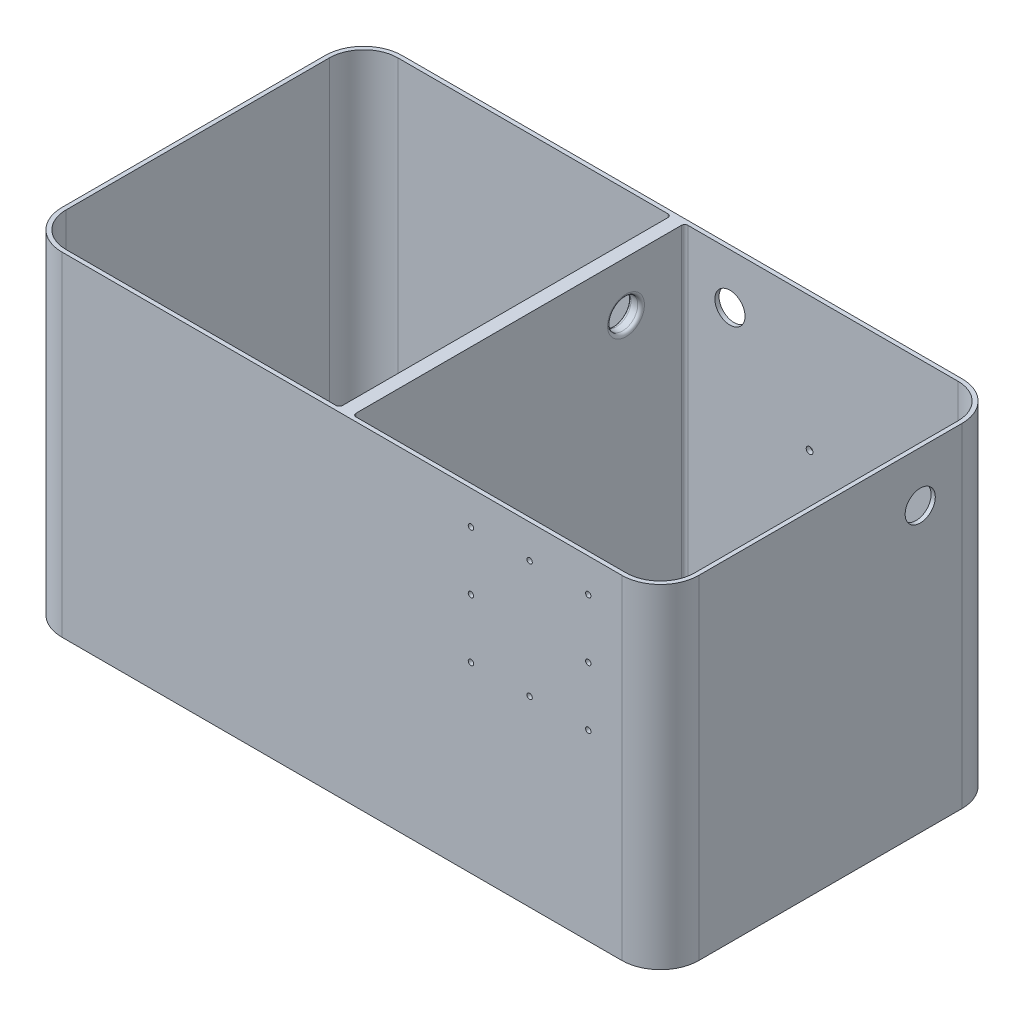
SolidWorks part; units mm, degrees
ref_plane "前视基准面" through (0, 0, 0) normal (0, 0, 1) x (1, 0, 0)
ref_plane "上视基准面" through (0, 0, 0) normal (0, 1, 0) x (1, 0, 0)
ref_plane "右视基准面" through (0, 0, 0) normal (1, 0, 0) x (0, 0, -1)
other "Configuration Table"
sketch "草图1" plane through (0, 0, 0) normal (0, 1, 0) x (1, 0, 0)
  line L1 (-167, 101.5) -> (167, 101.5)
  line L2 (-190, 78.5) -> (-190, -78.5)
  line L3 (-167, -101.5) -> (167, -101.5)
  line L4 (190, 78.5) -> (190, -78.5)
  line L5 (-190, 101.5) -> (190, -101.5) construction
  line L6 (-190, -101.5) -> (190, 101.5) construction
  arc A0 (167, -101.5) -> (190, -78.5) centre (167, -78.5) ccw
  arc A1 (167, 101.5) -> (190, 78.5) centre (167, 78.5) cw
  arc A2 (-190, -78.5) -> (-167, -101.5) centre (-167, -78.5) ccw
  arc A3 (-167, 101.5) -> (-190, 78.5) centre (-167, 78.5) ccw
  point P0 (0, 0)
  dimension "D3" = 23
  dimension "D1" = 380
  dimension "D2" = 203
extrude "凸台-拉伸1" add sketch "草图1" along normal blind 199
sketch "草图3" plane through (0, 199, 0) normal (0, 1, 0) x (1, 0, 0)
  line L0 (-190, 78.5) -> (-190, -78.5) construction
  line L1 (-167, 99) -> (167, 99)
  line L2 (-187.5, 78.5) -> (-187.5, -78.5)
  line L3 (-167, -99) -> (167, -99)
  line L4 (187.5, 78.5) -> (187.5, -78.5)
  line L5 (-187.5, 99) -> (187.5, -99) construction
  line L6 (-187.5, -99) -> (187.5, 99) construction
  line L7 (190, -78.5) -> (190, 78.5) construction
  arc A0 (-187.5, -78.5) -> (-167, -99) centre (-167, -78.5) ccw
  arc A1 (167, -99) -> (187.5, -78.5) centre (167, -78.5) ccw
  arc A2 (167, 99) -> (187.5, 78.5) centre (167, 78.5) cw
  arc A3 (-167, 99) -> (-187.5, 78.5) centre (-167, 78.5) ccw
  point P0 (0, 0)
  dimension "D5" = 20.5
  dimension "D1" = 198
  dimension "D2" = 375
  dimension "D3" = 2.5
  dimension "D4" = 2.5
extrude "切除-拉伸1" cut sketch "草图3" against normal blind 195
sketch "草图4" plane through (0, 4, 0) normal (0, 1, 0) x (1, 0, 0)
  line L0 (0, 99) -> (0, -99) construction
  line L1 (167, 99) -> (-167, 99) construction
  line L2 (-167, -99) -> (167, -99) construction
  line L3 (-4, 99) -> (-4, -99)
  line L4 (-167, -99) -> (167, -99) construction
  line L5 (4, 99) -> (4, -99)
  line L6 (-4, 99) -> (4, 99)
  line L7 (-4, -99) -> (4, -99)
  dimension "D1" = 4
extrude "凸台-拉伸2" add sketch "草图4" along normal blind 195
fillet "圆角1" radius 2 16 edges at (85.5, 4, 99) (181.4957, 4, 92.9957) (187.5, 4, 0) (181.4957, 4, -92.9957) (-85.5, 4, 99) (-181.4957, 4, 92.9957) (-187.5, 4, 0) (-181.4957, 4, -92.9957) (-4, 101.5, -99) (-4, 4, 0) (-4, 101.5, 99) (4, 101.5, 99) (4, 101.5, -99) (4, 4, 0) (85.5, 4, -99) (-85.5, 4, -99)
sketch "草图6" plane through (0, 0, -101.5) normal (0, 0, -1) x (-1, 0, 0)
  line L0 (0, 199) -> (0, 0) construction
  line L1 (-167, 199) -> (167, 199) construction
  line L2 (-6, 199) -> (-6, 0) construction
  line L4 (-167, 0) -> (167, 0) construction
  line L5 (6, 199) -> (6, 0) construction
  line L6 (-167, 199) -> (-167, 0) construction
  circle A0 centre (-155, 119) radius 2
  circle A1 centre (-155, 64) radius 2
  circle A2 centre (-78.5, 64) radius 2
  circle A3 centre (-78.5, 119) radius 2
  circle A4 centre (-31, 169) radius 9
  point P13 (-155, 119)
  point P14 (-155, 64)
  point P17 (-78.5, 119)
  point P18 (-78.5, 64)
  dimension "D5" = 4
  dimension "D6" = 4
  dimension "D7" = 4
  dimension "D8" = 4
  dimension "D10" = 18
  dimension "D1" = 12
  dimension "D2" = 12
  dimension "D3" = 76.5
  dimension "D4" = 55
  dimension "D9" = 80
  dimension "D11" = 25
  dimension "D12" = 30
extrude "切除-拉伸2" cut sketch "草图6" against normal up to next contours A2 | A3 | A0 | A1 | A4
sketch "草图7" plane through (4, 0, 0) normal (1, 0, 0) x (0, 0, -1)
  line L0 (99, 199) -> (99, 0) construction
  line L1 (78.5, 0) -> (101.5, 0) construction
  line L2 (-78.5, 199) -> (78.5, 199) construction
  circle A0 centre (64, 169) radius 9
  dimension "D2" = 18
  dimension "D1" = 35
  dimension "D3" = 30
extrude "切除-拉伸3" cut sketch "草图7" against normal up to next
fillet "圆角2" radius 2 2 edges at (-4, 169, -73) (4, 169, -73)
sketch "草图9" plane through (190, 0, 0) normal (1, 0, 0) x (0, 0, -1)
  line L0 (-78.5, 199) -> (78.5, 199) construction
  line L1 (78.5, 199) -> (78.5, 0) construction
  circle A0 centre (53.5, 169) radius 9
  dimension "D1" = 18
  dimension "D2" = 30
  dimension "D3" = 25
extrude "切除-拉伸4" cut sketch "草图9" against normal up to next
sketch "草图11" plane through (0, 0, 101.5) normal (0, 0, 1) x (1, 0, 0)
  line L0 (167, 199) -> (167, 0) construction
  line L1 (77, 179) -> (147, 179) construction
  line L2 (77, 179) -> (77, 109) construction
  line L3 (77, 109) -> (147, 109) construction
  line L4 (147, 179) -> (147, 109) construction
  line L5 (77, 179) -> (147, 109) construction
  line L6 (77, 109) -> (147, 179) construction
  line L7 (-167, 199) -> (167, 199) construction
  circle A0 centre (77, 179) radius 1.6
  circle A1 centre (147, 179) radius 1.6
  circle A2 centre (77, 109) radius 1.6
  circle A3 centre (147, 109) radius 1.6
  point P0 (112, 144)
  dimension "D5" = 3.2
  dimension "D6" = 3.2
  dimension "D7" = 3.2
  dimension "D8" = 3.2
  dimension "D1" = 70
  dimension "D2" = 70
  dimension "D3" = 20
  dimension "D4" = 20
extrude "切除-拉伸5" cut sketch "草图11" against normal up to next
sketch "草图12" plane through (0, 0, 101.5) normal (0, 0, 1) x (1, 0, 0)
  line L0 (77, 179) -> (147, 109) construction
  line L1 (77, 179) -> (147, 179) construction
  line L2 (77, 179) -> (77, 109) construction
  line L3 (77, 109) -> (147, 109) construction
  line L4 (147, 179) -> (147, 109) construction
  line L5 (77, 109) -> (147, 179) construction
  circle A1 centre (77, 144) radius 1.6
  circle A2 centre (112, 179) radius 1.6
  circle A3 centre (147, 144) radius 1.6
  circle A4 centre (112, 109) radius 1.6
  point P2 (112, 144)
  point P17 (112, 144)
  dimension "D2" = 3.2
  dimension "D1" = 35
  dimension "D4" = 70
  dimension "D5" = 70
  dimension "D3" = 4
extrude "切除-拉伸6" cut sketch "草图12" against normal up to next
